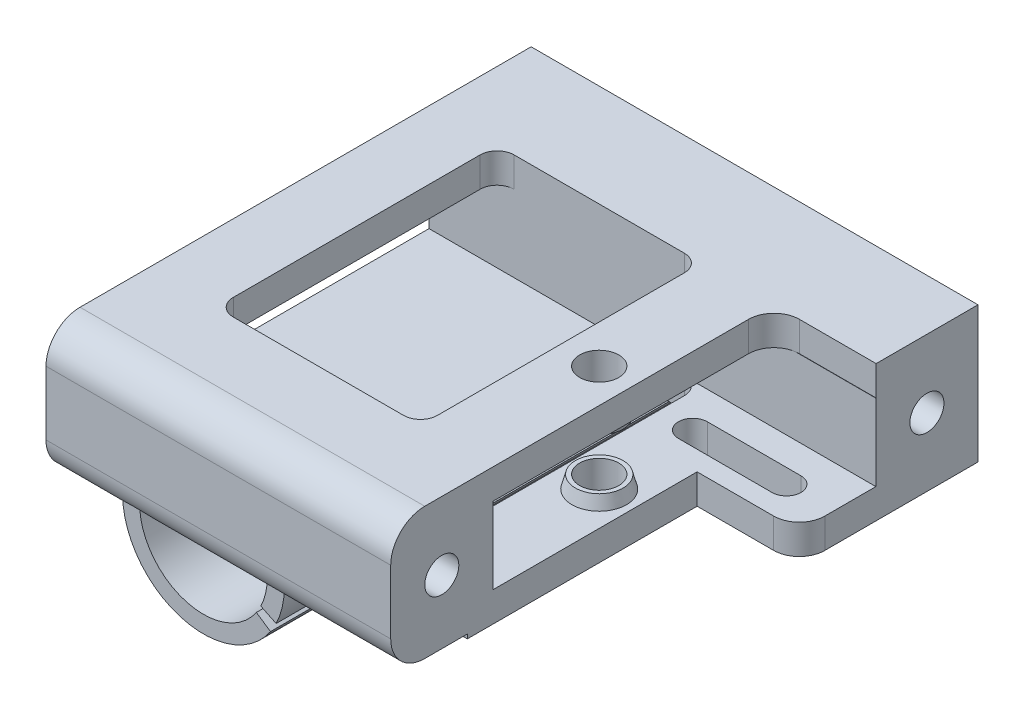
SolidWorks part; units mm, degrees
ref_plane "Front Plane" through (0, 0, 0) normal (0, 0, 1) x (1, 0, 0)
ref_plane "Top Plane" through (0, 0, 0) normal (0, 1, 0) x (1, 0, 0)
ref_plane "Right Plane" through (0, 0, 0) normal (1, 0, 0) x (0, 0, -1)
sketch "Sketch1" plane through (0, 0, 0) normal (0, 0, 1) x (1, 0, 0)
  line L0 (0, 0) -> (0, -31)
  line L1 (0, -31) -> (19, -31)
  line L2 (19, -31) -> (19, -16)
  line L3 (19, -16) -> (52.5, -16)
  line L4 (52.5, -16) -> (52.5, 0)
  line L5 (52.5, 0) -> (0, 0)
  line L6 (0, 0) -> (0.6966, -0.1385)
  dimension "D1" = 31
  dimension "D2" = 19
  dimension "D3" = 52.5
  dimension "D4" = 16
extrude "Boss-Extrude1" add sketch "Sketch1" along normal blind 57 contours L4 L5 L0 L1 L2 L3 region at (22.0067, -11.9267, 0)
ref_plane "Plane1" through (0, 0, 50) normal (0, 0, 1) x (1, 0, 0)
sketch "Sketch3" plane through (0, 0, 0) normal (-1, 0, 0) x (0, 0, 1)
  line L0 (57, 0) -> (0, 0) construction
  line L1 (12, -3.5) -> (45, -3.5)
  line L2 (12, -3.5) -> (12, -12.5)
  line L3 (12, -12.5) -> (45, -12.5)
  line L4 (45, -3.5) -> (45, -12.5)
  line L5 (57, -31) -> (48, -31)
  line L6 (57, -31) -> (57, -15.5)
  line L7 (57, -15.5) -> (48, -15.5)
  line L8 (48, -31) -> (48, -15.5)
  line L9 (0, 0) -> (0, -31) construction
  line L14 (57, -31) -> (0, -31) construction
  dimension "D1" = 9
  dimension "D2" = 33
  dimension "D3" = 3.5
  dimension "D4" = 12
  dimension "D5" = 15.5
  dimension "D6" = 9
extrude "Cut-Extrude2" cut sketch "Sketch3" against normal through all
fillet "Fillet1" radius 4 2 edges at (26.25, 0, 57) (26.25, -15.5, 57)
sketch "Sketch4" plane through (0, 0, 0) normal (0, 0, -1) x (-1, 0, 0)
  line L0 (-9.5, -21.5) -> (-9.5, -31) construction
  line L1 (0, -31) -> (-19, -31) construction
  line L2 (-15.7178, -25.6939) -> (-17.3759, -26.8123)
  line L3 (0, -31) -> (-19, -31)
  line L4 (0, -31) -> (0, -16)
  line L5 (0, -16) -> (-19, -16)
  line L6 (-19, -31) -> (-19, -16)
  line L7 (-16.241, -24.7878) -> (-18.0385, -25.6645)
  line L8 (-16.241, -24.7878) -> (-9.5, -21.5) construction
  circle A0 centre (-9.5, -21.5) radius 7.5
  circle A1 centre (-9.5, -21.5) radius 9.5
  line M8 (-19, -31) -> (0, -31)
  line M9 (0, -31) -> (0, 0)
  dimension "D1" = 15
  dimension "D2" = 19
  dimension "D3" = 8
  dimension "D4" = 64
extrude "Cut-Extrude3" cut sketch "Sketch4" against normal through all contours L5 A0 | L5 A0 | A1 L6 M8 | A1 L3 M9 | L7 A1 L2 A0 region at (16.8892, -25.7661, 0) region at (9.5, -22.0432, 0) region at (16.878, -28.878, 0) region at (2.122, -28.878, 0) region at (9.5, -15.1901, 0)
sketch "Sketch5" plane through (0, -16, 0) normal (0, -1, 0) x (1, 0, 0)
  line L0 (32, 28.5) -> (36, 28.5) construction
  line L1 (22, 45) -> (30, 45)
  line L2 (20, 43) -> (20, 14)
  line L3 (22, 12) -> (30, 12)
  line L4 (32, 43) -> (32, 14)
  line L5 (36, 17) -> (47, 17) construction
  line L6 (36, 18.7) -> (47, 18.7)
  line L7 (36, 15.3) -> (47, 15.3)
  line L8 (19, 48) -> (19, 0) construction
  line L9 (36, 28.5) -> (36, 17) construction
  line L10 (19, 0) -> (52.5, 0) construction
  line L11 (52.5, 0) -> (52.5, 18) construction
  line L12 (52.5, 48) -> (52.5, 0) construction
  line L13 (0, 57) -> (52.5, 57) construction
  line L14 (49.5, 18) -> (49.5, 21) construction
  line L15 (49.5, 21) -> (40.5, 21)
  line L16 (40.5, 21) -> (40.5, 57)
  line L18 (40.5, 57) -> (52.5, 57)
  line L19 (52.5, 57) -> (52.5, 18)
  arc A0 (20, 14) -> (22, 12) centre (22, 14) ccw
  arc A1 (30, 12) -> (32, 14) centre (30, 14) ccw
  arc A2 (32, 43) -> (30, 45) centre (30, 43) ccw
  arc A3 (22, 45) -> (20, 43) centre (22, 43) ccw
  circle A4 centre (36, 28.5) radius 2 construction
  arc A5 (36, 18.7) -> (36, 15.3) centre (36, 17) ccw
  arc A6 (47, 15.3) -> (47, 18.7) centre (47, 17) ccw
  arc A7 (52.5, 18) -> (49.5, 21) centre (49.5, 18) ccw
  point P17 (41.5, 17)
  point P33 (0, 0)
  point P38 (0, 0)
  point P39 (40.5, 57)
  line M12 (52.5, 0) -> (52.5, 48)
  dimension "D1" = 2
  dimension "D4" = 4
  dimension "D6" = 1.7
  dimension "D9" = 11.5
  dimension "D12" = 6
  dimension "D2" = 12
  dimension "D3" = 33
  dimension "D5" = 4
  dimension "D7" = 11
  dimension "D8" = 1
  dimension "D10" = 12
  dimension "D11" = 18
  dimension "D13" = 9
extrude "Cut-Extrude4" cut sketch "Sketch5" against normal up to surface (12.5 mm away) contours A4 | L7 A6 L6 A5 | A7 L16 L15 M12 | L19 L18 L16 | L2 A0 L3 A1 L4 A2 L1 A3 region at (41.5, -16, 17) region at (46.5237, -16, 38.9169) up to face at (26.25, -3.5, 28.5)
sketch "Sketch6" plane through (0, 0, 0) normal (0, 1, 0) x (1, 0, 0)
  line L0 (52.5, 0) -> (0, 0) construction
  line L1 (10, -12) -> (30, -12)
  line L2 (8, -14) -> (8, -43)
  line L3 (10, -45) -> (30, -45)
  line L4 (32, -14) -> (32, -43)
  line L5 (0, -53) -> (0, 0) construction
  line L6 (52.5, -56.9686) -> (40.5, -56.9686) construction
  line L7 (43.5, -11.9686) -> (52.5, -11.9686)
  line L8 (40.5, -14.9686) -> (40.5, -56.9686)
  line L9 (40.5, -56.9686) -> (52.5, -56.9686)
  line L10 (52.5, -11.9686) -> (52.5, -56.9686)
  line L11 (52.5, -53) -> (52.5, 0) construction
  line L12 (36, -28.5) -> (32, -28.5) construction
  arc A0 (10, -45) -> (8, -43) centre (10, -43) cw
  arc A1 (32, -43) -> (30, -45) centre (30, -43) cw
  arc A2 (32, -14) -> (30, -12) centre (30, -14) ccw
  arc A3 (10, -12) -> (8, -14) centre (10, -14) ccw
  arc A4 (43.5, -11.9686) -> (40.5, -14.9686) centre (43.5, -14.9686) ccw
  circle A5 centre (36, -28.5) radius 2 construction
  point P6 (8, -45)
  point P11 (32, -12)
  point P14 (8, -12)
  point P25 (40.5, -11.9686)
  dimension "D3" = 2
  dimension "D8" = 3
  dimension "D9" = 4
  dimension "D10" = 4
  dimension "D1" = 33
  dimension "D2" = 24
  dimension "D4" = 12
  dimension "D5" = 8
  dimension "D6" = 45
  dimension "D7" = 12
extrude "Cut-Extrude5" cut sketch "Sketch6" against normal up to surface (3.5 mm away) up to face at (31, -3.5, 37.9895)
sketch "Sketch9" plane through (0, -3.5, 0) normal (0, -1, 0) x (1, 0, 0)
  line L0 (40.5, 21) -> (40.5, 48) construction
  line L1 (19, 0) -> (52.5, 0) construction
  circle A0 centre (36.5, 28.5) radius 3.2
  dimension "D1" = 6.4
  dimension "D2" = 4
  dimension "D3" = 28.5
ref_plane "Plane3" through (0, -5, 0) normal (0, -1, 0) x (-1, 0, 0)
sketch "Sketch10" plane through (0, -5, 0) normal (0, -1, 0) x (-1, 0, 0)
  circle A0 centre (-36.5, -28.5) radius 2.8
  dimension "D1" = 5.6
loft "Loft1" add profiles "Sketch9", "Sketch10" connector at (36.5, -3.5, 25.3) connector at (36.5, -5, 25.7)
ref_plane "Plane4" through (0, -8, 0) normal (0, -1, 0) x (-1, 0, 0)
mirror "Mirror2" about plane through (0, -8, 0) normal (0, -1, 0) of "Loft1"
sketch "Sketch11" plane through (0, -11, 0) normal (0, 1, 0) x (1, 0, 0)
  circle A0 centre (36.5, -28.5) radius 2.3
  dimension "D1" = 4.6
extrude "Cut-Extrude6" cut sketch "Sketch11" against normal through all both and the other way through all
sketch "Sketch13" plane through (52.5, 0, 0) normal (1, 0, 0) x (0, 0, -1)
  line L0 (-51, -8) -> (-6, -8) construction
  line L1 (-6, -8) -> (0, -8) construction
  line L2 (0, -16) -> (0, 0) construction
  line L3 (-51, -8) -> (-57, -8) construction
  line L4 (-57, -4) -> (-57, -11.5) construction
  circle A0 centre (-6, -8) radius 2
  circle A1 centre (-51, -8) radius 2
  point P4 (-55.5043, -8)
  point P9 (-57, -8)
  dimension "D1" = 45
  dimension "D2" = 4
extrude "Cut-Extrude7" cut sketch "Sketch13" against normal blind 20
